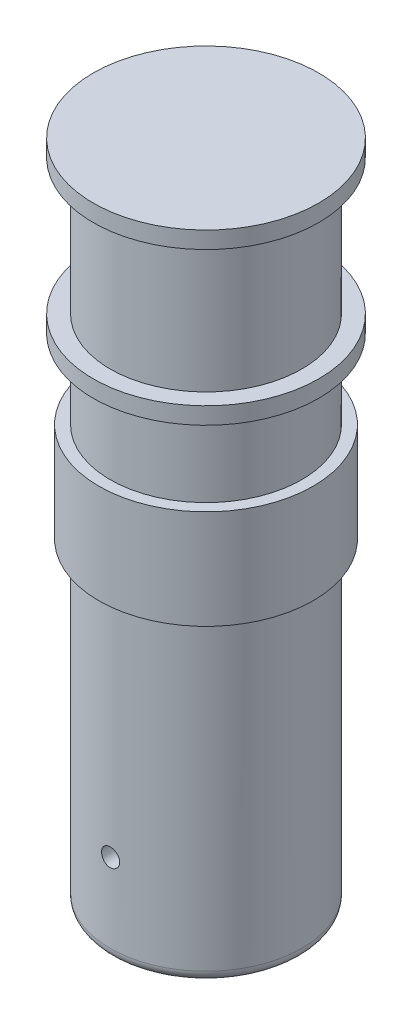
SolidWorks part; units mm, degrees
material "ABS"
ref_plane "Front Plane" through (0, 0, 0) normal (0, 0, 1) x (1, 0, 0)
ref_plane "Top Plane" through (0, 0, 0) normal (0, 1, 0) x (1, 0, 0)
ref_plane "Right Plane" through (0, 0, 0) normal (1, 0, 0) x (0, 0, -1)
sketch "Sketch1" plane through (0, 0, 0) normal (0, 0, 1) x (1, 0, 0)
  line L2 (-8.5, -44) -> (-8.5, -15.8)
  line L3 (-8.5, 0) -> (-10, 0)
  line L4 (-10, 0) -> (-10, 1.5)
  line L5 (-10, 1.5) -> (-8.5, 1.5)
  line L6 (-8.5, 1.5) -> (-8.5, 13.5)
  line L7 (-8.5, 13.5) -> (-10, 13.5)
  line L8 (-10, 13.5) -> (-10, 15)
  line L9 (-10, 15) -> (0, 15)
  line L10 (0, 15) -> (0, -30)
  line L11 (-4, -44) -> (-8.5, -44)
  line L12 (-4, -30) -> (-4, -44)
  line L13 (0, -30) -> (-4, -30)
  line L14 (-8.5, -15.8) -> (-9.5, -15.8)
  line L16 (-9.5, -15.8) -> (-9.5, -7)
  line L17 (-9.5, -7) -> (-8.5, -7)
  line L18 (-8.5, -7) -> (-8.5, 0)
  point P1 (0, 0)
  dimension "D1" = 8.5
  dimension "D2" = 1.5
  dimension "D3" = 44
  dimension "D4" = 1.5
  dimension "D5" = 4
  dimension "D6" = 14
  dimension "D7" = 15
  dimension "D8" = 10
  dimension "D9" = 28.2
  dimension "D10" = 1
  dimension "D11" = 7
revolve "Revolve1" add sketch "Sketch1" angle 360 about L10
fillet "Fillet1" radius 1 2 edges at (-8.5, -44, 0) (-4, -44, 0)
hole_wizard "M2x0.4 Tapped Hole1" positions "Sketch2" profile "Sketch3" tap size "M2x0.4" standard "ANSI Metric" end condition up to next
sketch "Sketch2" plane through (0, 0, 0) normal (0, 0, 1) x (1, 0, 0)
  line L0 (-7.5, -44) -> (7.5, -44) construction
  point P0 (0, -36)
  dimension "D1" = 8
sketch "Sketch3" plane through (0, -36, 0) normal (1, 0, 0) x (0, 1, 0)
  line L0 (0, 0) -> (0, 8.5)
  line L1 (0, 8.5) -> (0.8, 8.5)
  line L2 (0.8, 8.5) -> (0.8, 0)
  line L5 (0.8, 0) -> (0, 0)
  line L11 (0, -6.35) -> (0, 107.95) construction
  dimension "Thru Tap Drill Dia." = 1.6
  dimension "Thru Tap Drill Depth" = 8.5
cosmetic thread "Hole Thread1" parameters "D2"=2
